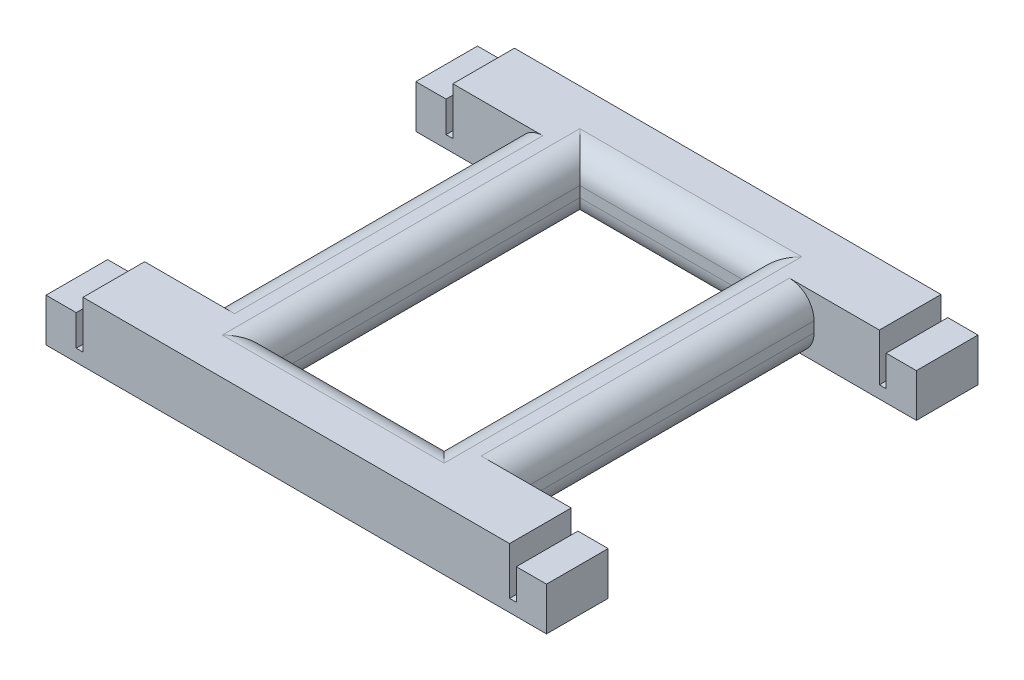
SolidWorks part; units mm, degrees
ref_plane "Front Plane" through (0, 0, 0) normal (0, 0, 1) x (1, 0, 0)
ref_plane "Top Plane" through (0, 0, 0) normal (0, 1, 0) x (1, 0, 0)
ref_plane "Right Plane" through (0, 0, 0) normal (1, 0, 0) x (0, 0, -1)
ref_axis "X Axis" through (-39.3295, 0, 0) along (1, 0, 0)
ref_axis "Y Axis" through (0, 0, -37.7472) along (0, 0, 1)
ref_axis "Z Axis" through (0, 35.6627, 0) along (0, -1, 0)
sketch "Sketch1" plane through (0, 0, 0) normal (0, 1, 0) x (1, 0, 0)
  line L0 (0, 75) -> (0, -75) construction
  line L1 (-60, 62.5) -> (-60, -62.5)
  line L2 (-86.5, 62.5) -> (-60, 62.5)
  line L3 (-86.5, 62.5) -> (-86.5, 87.5)
  line L4 (-86.5, 87.5) -> (86.5, 87.5)
  line L5 (86.5, 62.5) -> (86.5, 87.5)
  line L6 (-86.5, 62.5) -> (86.5, 87.5) construction
  line L7 (-86.5, 87.5) -> (86.5, 62.5) construction
  line L8 (-86.5, -87.5) -> (86.5, -87.5)
  line L9 (-86.5, -87.5) -> (-86.5, -62.5)
  line L10 (-86.5, -62.5) -> (-60, -62.5)
  line L11 (86.5, -87.5) -> (86.5, -62.5)
  line L12 (-86.5, -87.5) -> (86.5, -62.5) construction
  line L13 (-86.5, -62.5) -> (86.5, -87.5) construction
  line L14 (-35, 62.5) -> (-35, -62.5)
  line L15 (35, 62.5) -> (35, -62.5)
  line L16 (60, 62.5) -> (60, -62.5)
  line L17 (-60, 0) -> (60, 0) construction
  line L18 (-35, 62.5) -> (35, 62.5)
  line L19 (60, 62.5) -> (86.5, 62.5)
  line L20 (60, -62.5) -> (86.5, -62.5)
  line L21 (-35, -62.5) -> (35, -62.5)
  point P2 (0, 0)
  point P22 (0, 0)
  dimension "D1" = 150
  dimension "D2" = 173
  dimension "D3" = 25
  dimension "D4" = 25
  dimension "D5" = 25
  dimension "D6" = 120
extrude "Boss-Extrude1" add sketch "Sketch1" against normal blind 5 and the other way blind 19.25
sketch "Sketch2" plane through (0, -5, 0) normal (0, 1, 0) x (1, 0, 0)
  line L0 (86.5, -87.5) -> (86.5, -62.5) construction
  line L1 (-86.5, 87.5) -> (-101.5, 87.5)
  line L2 (-86.5, 87.5) -> (-86.5, 62.5)
  line L3 (-86.5, 62.5) -> (-101.5, 62.5)
  line L4 (-101.5, 87.5) -> (-101.5, 62.5)
  line L5 (86.5, 87.5) -> (101.5, 87.5)
  line L6 (86.5, 87.5) -> (86.5, 62.5)
  line L7 (86.5, 62.5) -> (101.5, 62.5)
  line L8 (101.5, 87.5) -> (101.5, 62.5)
  line L9 (-86.5, -62.5) -> (-101.5, -62.5)
  line L10 (-86.5, -62.5) -> (-86.5, -87.5)
  line L11 (-86.5, -87.5) -> (-101.5, -87.5)
  line L12 (-101.5, -62.5) -> (-101.5, -87.5)
  line L13 (86.5, -62.5) -> (101.5, -62.5)
  line L14 (86.5, -62.5) -> (86.5, -87.5)
  line L15 (86.5, -87.5) -> (101.5, -87.5)
  line L16 (101.5, -62.5) -> (101.5, -87.5)
  point P4 (86.5, -87.5)
  point P26 (86.5, -87.5)
  dimension "D1" = 15
extrude "Boss-Extrude2" add sketch "Sketch2" along normal up to surface (5 mm away) up to plane "Top Plane"
sketch "Sketch3" plane through (0, 0, 0) normal (0, 1, 0) x (1, 0, 0)
  line L0 (-101.5, 62.5) -> (-86.5, 62.5) construction
  line L1 (-101.5, 87.5) -> (-89.25, 87.5)
  line L2 (-101.5, 87.5) -> (-101.5, 62.5)
  line L3 (-101.5, 62.5) -> (-89.25, 62.5)
  line L4 (-89.25, 87.5) -> (-89.25, 62.5)
  line L5 (-86.5, 62.5) -> (-86.5, 87.5) construction
  line L6 (101.5, 87.5) -> (89.25, 87.5)
  line L7 (101.5, 87.5) -> (101.5, 62.5)
  line L8 (101.5, 62.5) -> (89.25, 62.5)
  line L9 (89.25, 87.5) -> (89.25, 62.5)
  line L10 (-101.5, -62.5) -> (-89.25, -62.5)
  line L11 (-101.5, -62.5) -> (-101.5, -87.5)
  line L12 (-101.5, -87.5) -> (-89.25, -87.5)
  line L13 (-89.25, -62.5) -> (-89.25, -87.5)
  line L14 (101.5, -62.5) -> (89.25, -62.5)
  line L15 (101.5, -62.5) -> (101.5, -87.5)
  line L16 (101.5, -87.5) -> (89.25, -87.5)
  line L17 (89.25, -62.5) -> (89.25, -87.5)
  point P11 (106.5, -87.5)
  dimension "D1" = 2.75
extrude "Boss-Extrude3" add sketch "Sketch3" along normal blind 12.5
fillet "Fillet1" radius 10 12 edges at (0, 19.25, 62.5) (60, 19.25, 0) (35, 19.25, 0) (-60, 19.25, 0) (-35, 19.25, 0) (0, 19.25, -62.5) (0, -5, 62.5) (-35, -5, 0) (0, -5, -62.5) (35, -5, 0) (60, -5, 0) (-60, -5, 0)
